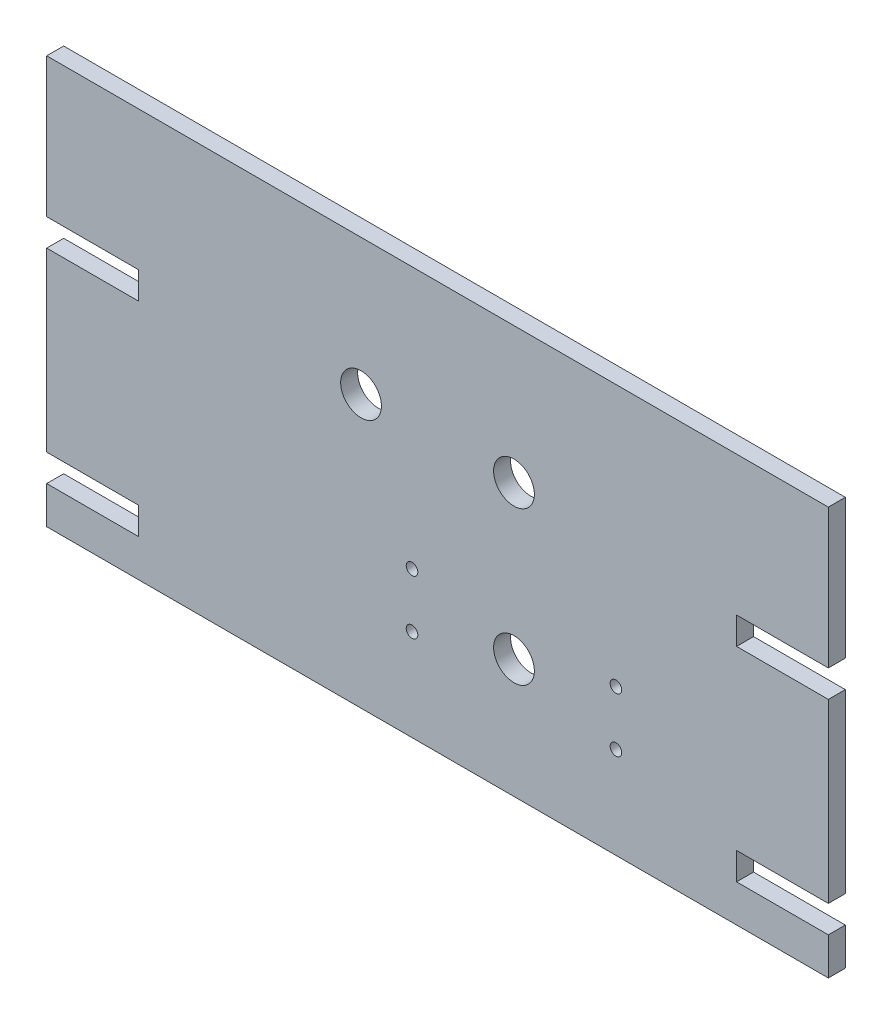
SolidWorks part; units mm, degrees
ref_plane "Front Plane" through (0, 0, 0) normal (0, 0, 1) x (1, 0, 0)
ref_plane "Top Plane" through (0, 0, 0) normal (0, 1, 0) x (1, 0, 0)
ref_plane "Right Plane" through (0, 0, 0) normal (1, 0, 0) x (0, 0, -1)
sketch "Sketch1" plane through (0, 0, 0) normal (0, 0, 1) x (1, 0, 0)
  line L1 (-115, -60) -> (115, -60)
  line L2 (-115, -60) -> (-115, 60)
  line L3 (-115, 60) -> (115, 60)
  line L4 (115, -60) -> (115, 60)
  line L5 (-115, -60) -> (115, 60) construction
  line L6 (-115, 60) -> (115, -60) construction
  point P0 (0, 0)
  dimension "D1" = 230
  dimension "D2" = 120
extrude "Boss-Extrude1" add sketch "Sketch1" along normal blind 5
sketch "Sketch2" plane through (0, 0, 0) normal (0, 0, -1) x (-1, 0, 0)
  line L0 (115, 11) -> (88, 11)
  line L1 (115, 60) -> (115, -60) construction
  line L2 (88, 11) -> (88, 19)
  line L3 (88, 19) -> (115, 19)
  line L4 (115, 19) -> (115, 11)
  line L5 (117.8, 19) -> (115.5, 19) construction
  line L6 (115.5, 11) -> (117.8, 11) construction
  line L7 (115, -49) -> (88, -49)
  line L8 (88, -41) -> (115, -41)
  line L9 (88, -49) -> (88, -41)
  line L10 (115, -41) -> (115, -49)
  line L11 (115.5, -49) -> (117.8, -49) construction
  line L12 (117.8, -41) -> (115.5, -41) construction
  line L13 (115, -40.5) -> (115, -30.5) construction
  line L14 (0, 2.75) -> (0, -2.75) construction
  line L15 (-115, -41) -> (-115, -49)
  line L16 (-88, -49) -> (-88, -41)
  line L17 (-88, -41) -> (-115, -41)
  line L18 (-115, -49) -> (-88, -49)
  line L19 (-115, 19) -> (-115, 11)
  line L20 (-88, 19) -> (-115, 19)
  line L21 (-88, 11) -> (-88, 19)
  line L22 (-115, 11) -> (-88, 11)
  dimension "D1" = 27
  dimension "D2" = 27
extrude "Cut-Extrude1" cut sketch "Sketch2" against normal up to next
sketch "Sketch3" plane through (0, 0, 5) normal (0, 0, 1) x (1, 0, 0)
  line L0 (-115, 20) -> (115, 20) construction
  line L1 (-115, 60) -> (-115, 19) construction
  line L2 (115, 19) -> (115, 60) construction
  line L3 (115, 60) -> (-115, 60) construction
  line L4 (22.5, 60) -> (22.5, -60) construction
  line L5 (-115, -60) -> (115, -60) construction
  circle A0 centre (22.5, 20) radius 6
  circle A1 centre (-22.5, 20) radius 6
  circle A2 centre (22.5, -25) radius 6
  dimension "D2" = 12
  dimension "D3" = 45
  dimension "D1" = 40
  dimension "D4" = 45
  dimension "D5" = 22.5
extrude "Cut-Extrude2" cut sketch "Sketch3" against normal up to next
sketch "Sketch5" plane through (0, 0, 5) normal (0, 0, 1) x (1, 0, 0)
  line L1 (-7.5, -33) -> (52.5, -33)
  line L2 (-7.5, -33) -> (-7.5, -17)
  line L3 (-7.5, -17) -> (52.5, -17)
  line L4 (52.5, -33) -> (52.5, -17)
  line L5 (-7.5, -33) -> (52.5, -17) construction
  line L6 (-7.5, -17) -> (52.5, -33) construction
  point P0 (22.5, -25)
  dimension "D1" = 16
  dimension "D2" = 60
hole_wizard "M3 Clearance Hole1" positions "3DSketch1" profile "Sketch6" hole size "M3" standard "ISO" end condition through all
sketch3d "3DSketch1"
  point P0 (-7.5, -17, 5)
  point P3 (52.5, -17, 5)
  point P6 (52.5, -33, 5)
  point P9 (-7.5, -33, 5)
sketch "Sketch6" plane through (-7.5, -17, 5) normal (1, 0, 0) x (0, -1, 0)
  line L0 (0, 0) -> (0, 5)
  line L1 (0, 5) -> (1.7, 5)
  line L2 (1.7, 5) -> (1.7, 0)
  line L5 (1.7, 0) -> (0, 0)
  line L11 (0, -6.35) -> (0, 107.95) construction
  dimension "Thru Hole Dia." = 3.4
  dimension "Thru Hole Depth" = 5
